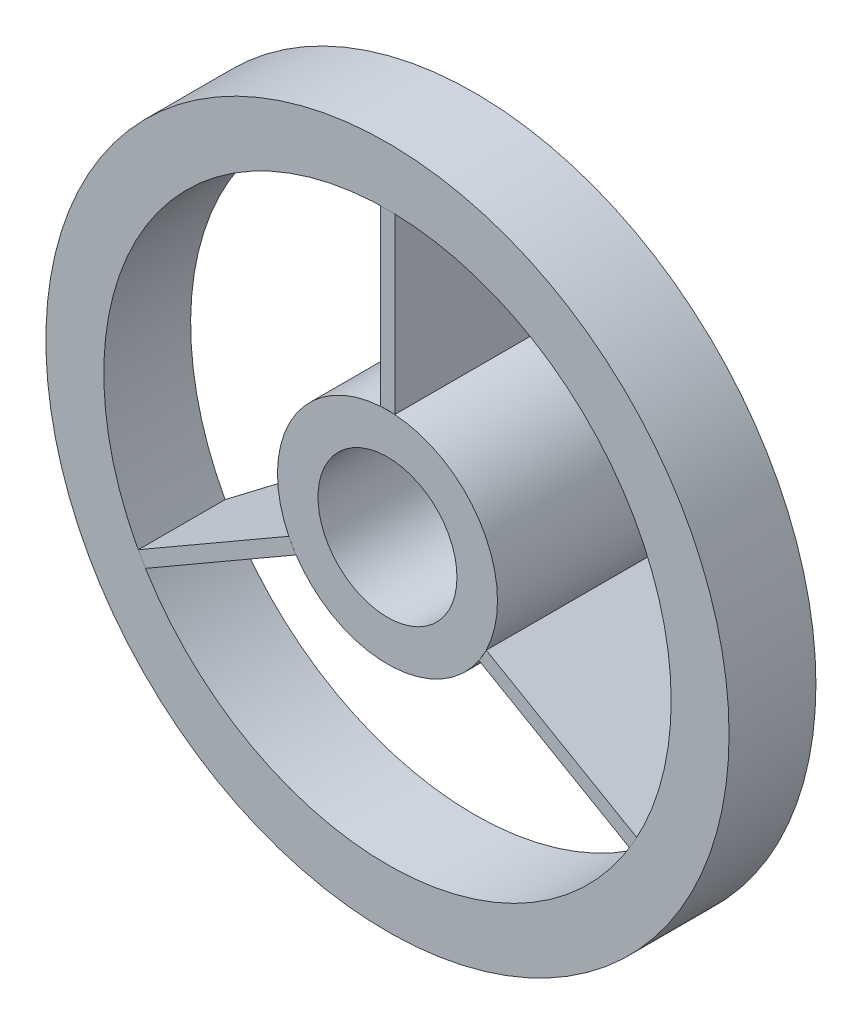
SolidWorks part; units mm, degrees
ref_plane "Front Plane" through (0, 0, 0) normal (0, 0, 1) x (1, 0, 0)
ref_plane "Top Plane" through (0, 0, 0) normal (0, 1, 0) x (1, 0, 0)
ref_plane "Right Plane" through (0, 0, 0) normal (1, 0, 0) x (0, 0, -1)
sketch "Sketch1" plane through (0, 0, 0) normal (0, 0, 1) x (1, 0, 0)
  circle A0 centre (0, 0) radius 1.2
  circle A1 centre (0, 0) radius 1.9
  dimension "D1" = 2.4
  dimension "D2" = 0.7
extrude "Boss-Extrude1" add sketch "Sketch1" along normal blind 3.5
sketch "Sketch2" plane through (0, 0, 3.5) normal (0, 0, 1) x (1, 0, 0)
  circle A0 centre (0, 0) radius 4.9
  circle A1 centre (0, 0) radius 5.9
  dimension "D1" = 9.8
  dimension "D2" = 1
extrude "Boss-Extrude2" add sketch "Sketch2" against normal blind 1.5 separate body
sketch "Sketch7" plane through (0, 0, 0) normal (1, 0, 0) x (0, 0, -1)
  line L0 (-3.4985, 1.8988) -> (-3.4985, 4.9067)
  line L1 (-3.4985, 4.9067) -> (-2.0035, 4.9067)
  line L2 (-2.0035, 4.9067) -> (0, 1.8988)
  line L5 (-3.4985, 1.8988) -> (-3.4985, 1.6988)
  line L6 (-3.4985, 1.6988) -> (0, 1.6988)
  line L7 (0, 1.6988) -> (0, 1.8988)
  dimension "D1" = 0.2
extrude "Boss-Extrude3" add sketch "Sketch7" along normal mid plane 0.25
ref_axis "Axis1" through (0, 0, 3.5) along (0, 0, -1)
pattern_circular "CirPattern1" count 3 over 360 about axis through (0, 0, 3.5) along (0, 0, -1) of "Boss-Extrude3"
